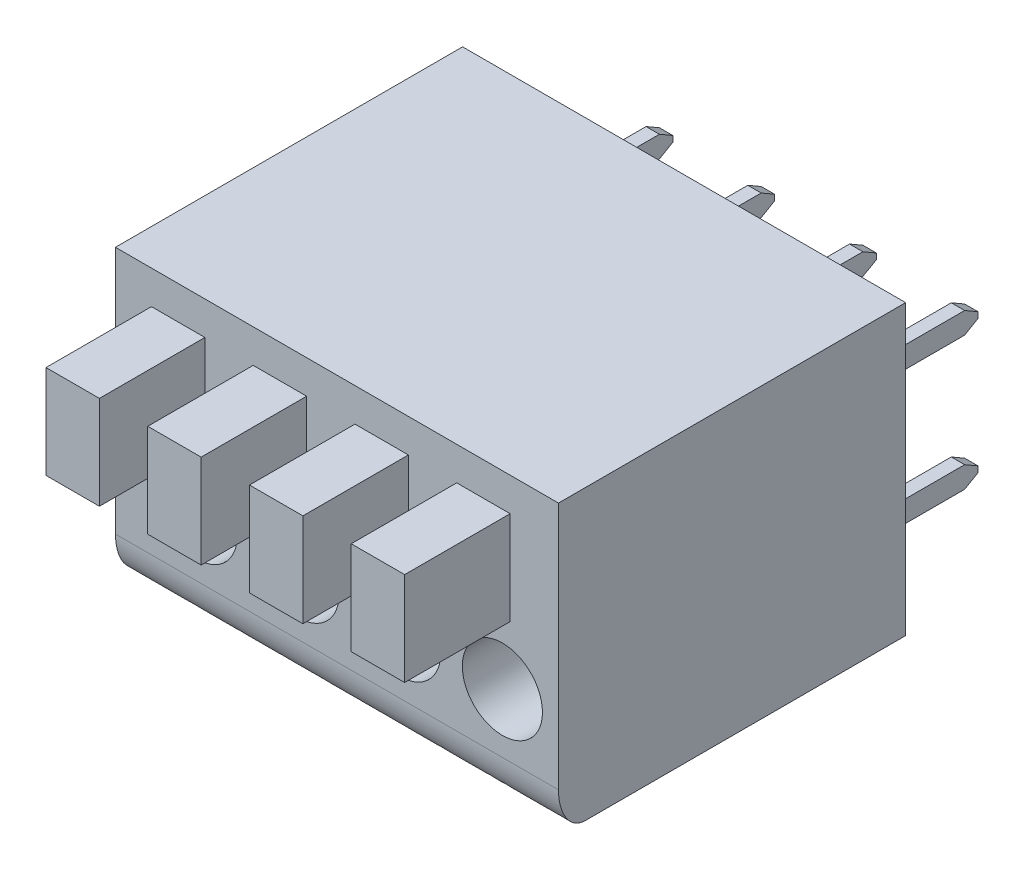
SolidWorks part; units mm, degrees
ref_plane "Спереди" through (0, 0, 0) normal (0, 0, 1) x (1, 0, 0)
ref_plane "Сверху" through (0, 0, 0) normal (0, 1, 0) x (1, 0, 0)
ref_plane "Справа" through (0, 0, 0) normal (1, 0, 0) x (0, 0, -1)
sketch "Эскиз1" plane through (0, 0, 0) normal (0, 0, 1) x (1, 0, 0)
  line L1 (-8.295, -5.4) -> (8.295, -5.4)
  line L2 (-8.295, -5.4) -> (-8.295, 5.4)
  line L3 (-8.295, 5.4) -> (8.295, 5.4)
  line L4 (8.295, -5.4) -> (8.295, 5.4)
  line L5 (-8.295, -5.4) -> (8.295, 5.4) construction
  line L6 (-8.295, 5.4) -> (8.295, -5.4) construction
  point P0 (0, 0)
  dimension "D1" = 16.59
  dimension "D2" = 10.8
extrude "Бобышка-Вытянуть1" add sketch "Эскиз1" along normal blind 13
fillet "Скругление1" radius 1 1 edges at (0, -5.4, 13) second distance 1.5 first distance on face at (0, -5.4, 6.5)
sketch "Эскиз2" plane through (0, 0, 13) normal (0, 0, 1) x (1, 0, 0)
  line L0 (8.295, -3.9) -> (8.295, 5.4) construction
  line L1 (4.485, 0.65) -> (6.485, 0.65)
  line L2 (4.485, 0.65) -> (4.485, 4.15)
  line L3 (4.485, 4.15) -> (6.485, 4.15)
  line L4 (6.485, 0.65) -> (6.485, 4.15)
  line L5 (4.485, 0.65) -> (6.485, 4.15) construction
  line L6 (4.485, 4.15) -> (6.485, 0.65) construction
  line L7 (8.295, 5.4) -> (-8.295, 5.4) construction
  point P0 (5.485, 2.4)
  dimension "D1" = 3.5
  dimension "D2" = 2
  dimension "D3" = 3.81
  dimension "D4" = 4.75
extrude "Бобышка-Вытянуть2" add sketch "Эскиз2" along normal blind 3.95
sketch "Эскиз3" plane through (0, 0, 13) normal (0, 0, 1) x (1, 0, 0)
  line L0 (8.295, -3.9) -> (8.295, 5.4) construction
  circle A0 centre (6.195, -1.686) radius 1.5
  dimension "D1" = 3
  dimension "D2" = 2.1
extrude "Вырез-Вытянуть1" cut sketch "Эскиз3" against normal blind 3.95
sketch "Эскиз4" plane through (0, 0, 0) normal (0, 0, -1) x (-1, 0, 0)
  line L0 (-8.295, 5.4) -> (8.295, 5.4) construction
  line L1 (-7.505, 2.45) -> (-7.005, 2.45)
  line L2 (-7.505, 2.45) -> (-7.505, 3.25)
  line L3 (-7.505, 3.25) -> (-7.005, 3.25)
  line L4 (-7.005, 2.45) -> (-7.005, 3.25)
  line L5 (-7.505, 2.45) -> (-7.005, 3.25) construction
  line L6 (-7.505, 3.25) -> (-7.005, 2.45) construction
  line L7 (-7.005, -1.75) -> (-7.505, -1.75)
  line L8 (-7.005, -1.75) -> (-7.005, -2.55)
  line L9 (-7.005, -2.55) -> (-7.505, -2.55)
  line L10 (-7.505, -1.75) -> (-7.505, -2.55)
  line L11 (-7.005, -1.75) -> (-7.505, -2.55) construction
  line L12 (-7.005, -2.55) -> (-7.505, -1.75) construction
  line L14 (-8.295, -5.4) -> (-8.295, 5.4) construction
  point P0 (-7.255, 2.85)
  point P5 (-7.255, -2.15)
  dimension "D1" = 0.5
  dimension "D2" = 0.8
  dimension "D3" = 5
  dimension "D4" = 2.55
  dimension "D5" = 1.04
extrude "Бобышка-Вытянуть3" add sketch "Эскиз4" along normal blind 3.5
chamfer "Фаска1" distance 0.5 angle 30 4 edges at (7.255, -2.55, -3.5) (7.255, -1.75, -3.5) (7.255, 2.45, -3.5) (7.255, 3.25, -3.5) first distance on face at (7.255, -2.55, -1.75) first distance on face at (7.255, -1.75, -1.75) first distance on face at (7.255, 2.45, -1.75) first distance on face at (7.255, 3.25, -1.75)
pattern_linear "Линейный массив2" count 4 spacing 3.81 along (-1, 0, 0) of "Бобышка-Вытянуть2", "Вырез-Вытянуть1", "Бобышка-Вытянуть3", "Фаска1"
